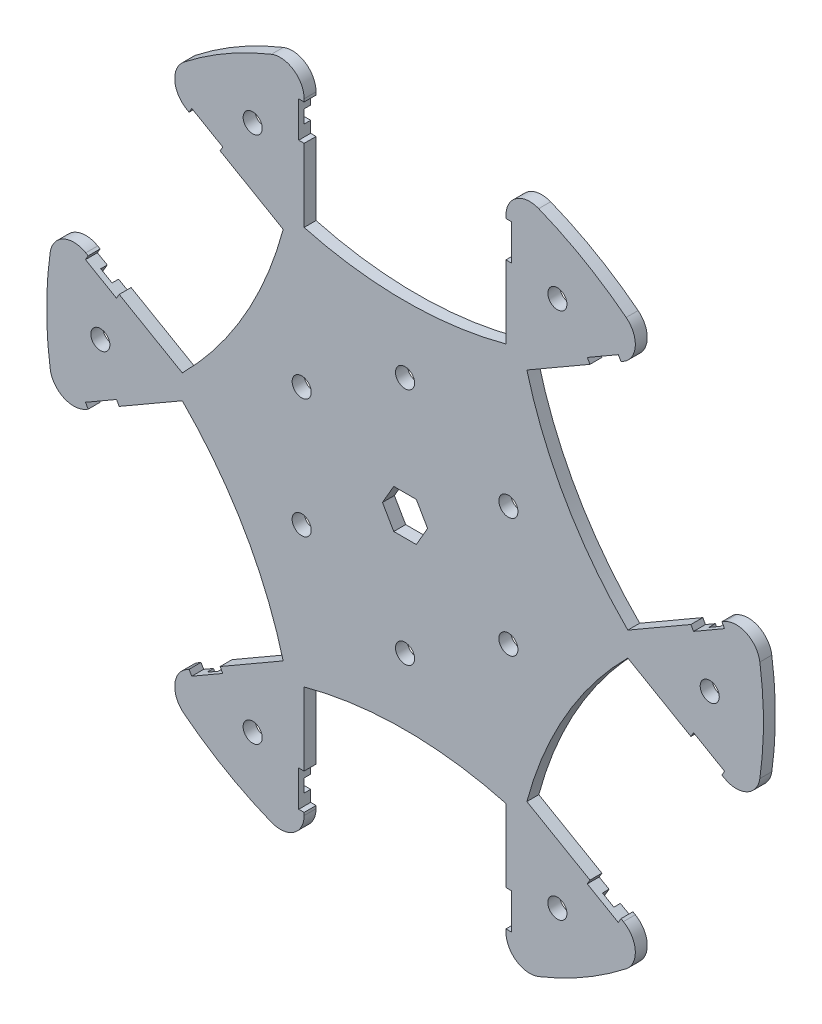
SolidWorks part; units mm, degrees
material "PET"
ref_plane "Front Plane" through (0, 0, 0) normal (0, 0, 1) x (1, 0, 0)
ref_plane "Top Plane" through (0, 0, 0) normal (0, 1, 0) x (1, 0, 0)
ref_plane "Right Plane" through (0, 0, 0) normal (1, 0, 0) x (0, 0, -1)
ref_axis "Axis1" through (0, 0, -6.4917) along (0, 0, 1)
sketch "Sketch2" plane through (0, 0, 0) normal (0, 0, 1) x (1, 0, 0)
  line L6 (56.0628, 0) -> (28.0314, 48.5518)
  line L7 (28.0314, 48.5518) -> (-28.0314, 48.5518)
  line L8 (-28.0314, 48.5518) -> (-56.0628, 0)
  line L9 (-56.0628, 0) -> (-28.0314, -48.5518)
  line L10 (-28.0314, -48.5518) -> (28.0314, -48.5518)
  line L11 (28.0314, -48.5518) -> (56.0628, 0)
  line L12 (56.0628, 0) -> (28.0314, 48.5518)
  line L13 (28.0314, 48.5518) -> (-28.0314, 48.5518)
  line L14 (-28.0314, 48.5518) -> (-56.0628, 0)
  line L15 (-56.0628, 0) -> (-28.0314, -48.5518)
  line L16 (-28.0314, -48.5518) -> (28.0314, -48.5518)
  line L17 (28.0314, -48.5518) -> (56.0628, 0)
  circle A0 centre (0, 0) radius 56.0628 construction
  circle A1 centre (0, 0) radius 56.0628
  circle A2 centre (0, 0) radius 63.4125 construction
  circle A3 centre (0, 0) radius 63.4125
  circle A4 centre (0, 0) radius 65 construction
  circle A5 centre (0, 0) radius 65
  dimension "D1" = 0
sketch "Sketch5" plane through (0, 0, 0) normal (0, 0, 1) x (1, 0, 0)
  line L0 (16.4124, 34.2097) -> (16.4124, 62.8938) construction
  line L1 (16.4124, 34.2097) -> (16.4124, 62.8938)
  line L2 (-16.4124, 62.8938) -> (-16.4124, 34.2097) construction
  line L3 (-16.4124, 62.8938) -> (-16.4124, 34.2097)
  line L4 (0, 48.5518) -> (0, 63.4125) construction
  line L5 (0, 48.5518) -> (0, 63.4125)
  arc A0 (-16.4124, 34.2097) -> (16.4124, 34.2097) centre (0, 97.1035) ccw construction
  arc A1 (-16.4124, 34.2097) -> (16.4124, 34.2097) centre (0, 97.1035) ccw
sketch "Sketch3" plane through (0, 0, 0) normal (0, 0, 1) x (1, 0, 0)
  circle A0 centre (0, 0) radius 60.0628
  circle A1 centre (0, 0) radius 56.0628 construction
  circle A2 centre (0, 0) radius 56.0628 construction
  dimension "D1" = 4
extrude "Disk" add sketch "Sketch3" along normal blind 2
sketch "Sketch4" plane through (0, 0, 0) normal (0, 0, 1) x (1, 0, 0)
  line L0 (28.0314, 48.5518) -> (-28.0314, 48.5518) construction
  line L1 (28.0314, 48.5518) -> (-28.0314, 48.5518) construction
  line L3 (-25.2, 49.6518) -> (25.2, 49.6518)
  line L4 (-25.2, 49.6518) -> (-25.2, 47.4518)
  line L5 (-25.2, 47.4518) -> (25.2, 47.4518)
  line L6 (25.2, 49.6518) -> (25.2, 47.4518)
  line L7 (-25.2, 49.6518) -> (25.2, 47.4518) construction
  line L8 (-25.2, 47.4518) -> (25.2, 49.6518) construction
  point P2 (0, 48.5518)
  dimension "D1" = 2.2
  dimension "D2" = 50.4
extrude "Axle" cut sketch "Sketch4" along normal blind 1.1
sketch "Sketch7" plane through (0, 0, 0) normal (0, 0, 1) x (1, 0, 0)
  line L0 (16.9124, 62.8938) -> (-16.9124, 62.8938)
  line L1 (0, 48.5518) -> (0, 63.4125) construction
  line L2 (16.9124, 62.8938) -> (16.9124, 33.3423)
  line L3 (-16.9124, 62.8938) -> (-16.9124, 33.3423)
  line L4 (-16.4124, 62.8938) -> (-16.4124, 34.2097) construction
  arc A0 (-16.9124, 33.3423) -> (16.9124, 33.3423) centre (0, 96.1035) ccw
  arc A1 (-16.4124, 34.2097) -> (16.4124, 34.2097) centre (0, 97.1035) ccw construction
  arc A2 (-16.4124, 34.2097) -> (16.4124, 34.2097) centre (0, 97.1035) ccw construction
  point P3 (0, 62.8938)
  point P6 (0, 32.1035)
  point P16 (0, 31.1035)
  dimension "D1" = 0.5
  dimension "D3" = 1
  dimension "D2" = 2
extrude "Roller" cut sketch "Sketch7" along normal up to next
sketch "Sketch8" plane through (0, 0, 0) normal (0, 0, 1) x (1, 0, 0)
  line L0 (16.9124, 47.4518) -> (16.9124, 49.6518) construction
  line L1 (16.9124, 47.4518) -> (16.9124, 49.6518) construction
  line L3 (-17.8124, 51.5518) -> (-16.9124, 51.5518)
  line L4 (17.8124, 51.5518) -> (17.8124, 45.5518)
  line L6 (16.9124, 51.5518) -> (16.4124, 51.5518)
  line L8 (16.4124, 51.5518) -> (16.4124, 45.5518)
  line L11 (16.4124, 34.2097) -> (16.4124, 62.8938) construction
  line L12 (16.4124, 34.2097) -> (16.4124, 62.8938) construction
  line L14 (-16.9124, 51.5518) -> (-16.4124, 51.5518)
  line L15 (16.9124, 51.5518) -> (16.9124, 45.5518) construction
  line L16 (16.9124, 33.3423) -> (16.9124, 47.4518) construction
  line L17 (17.8124, 51.5518) -> (16.9124, 51.5518)
  line L18 (17.8124, 45.5518) -> (16.9124, 45.5518)
  line L19 (16.4124, 45.5518) -> (16.9124, 45.5518)
  line L20 (0, 48.5518) -> (0, 63.4125) construction
  line L21 (0, 48.5518) -> (0, 63.4125) construction
  line L22 (-16.4124, 51.5518) -> (-16.4124, 45.5518)
  line L23 (-16.4124, 45.5518) -> (-16.9124, 45.5518)
  line L24 (-17.8124, 45.5518) -> (-16.9124, 45.5518)
  line L25 (-17.8124, 51.5518) -> (-17.8124, 45.5518)
  point P12 (16.9124, 48.5518)
  dimension "D1" = 6
  dimension "D2" = 1.4
extrude "Washer" cut sketch "Sketch8" along normal up to next
fillet "Fillet1" radius 4 2 edges at (16.9124, 57.6325, 1) (-16.9124, 57.6325, 1)
pattern_circular "CirPattern1" count 6 over 360 about axis through (0, 0, -6.4917) along (0, 0, 1) of "Axle", "Roller", "Washer", "Fillet1"
sketch "Sketch9" plane through (0, 0, 2) normal (0, 0, 1) x (1, 0, 0)
  line L0 (0, 0) -> (-30.0314, -52.0159) construction
  arc A0 (41.455, 43.4628) -> (16.9124, 57.6325) centre (0, 0) ccw construction
  circle A1 centre (-25.5314, -44.2216) radius 1.6
  dimension "D1" = 3.2
  dimension "D2" = 9
extrude "Roller screw" cut sketch "Sketch9" against normal up to next
pattern_circular "CirPattern3" count 6 over 360 about axis through (0, 0, -6.4917) along (0, 0, 1) of "Roller screw"
sketch "Sketch10" plane through (0, 0, 0) normal (0, 0, 1) x (1, 0, 0)
  line L0 (0, 0) -> (3.7816, 0) construction
  line L1 (3.7816, 0) -> (1.8908, 3.275)
  line L2 (1.8908, 3.275) -> (-1.8908, 3.275)
  line L3 (-1.8908, 3.275) -> (-3.7816, 0)
  line L4 (-3.7816, 0) -> (-1.8908, -3.275)
  line L5 (-1.8908, -3.275) -> (1.8908, -3.275)
  line L6 (1.8908, -3.275) -> (3.7816, 0)
  line L7 (0, 0) -> (0, 3.275) construction
  circle A0 centre (0, 0) radius 3.275 construction
  dimension "D1" = 6.55
  dimension "D2" = 90
extrude "Hex axle" cut sketch "Sketch10" along normal up to next
sketch "Sketch11" plane through (0, 0, 0) normal (0, 0, 1) x (1, 0, 0)
  line L0 (0, 0) -> (0, 20) construction
  line L1 (0, 0) -> (20, 0) construction
  circle A0 centre (0, 0) radius 20 construction
  circle A1 centre (0, 20) radius 1.6
  dimension "D1" = 3.2
  dimension "D2" = 40
  dimension "D3" = 90
extrude "Hub screws" cut sketch "Sketch11" along normal up to next
pattern_circular "CirPattern4" count 6 over 360 about axis through (0, 0, -6.4917) along (0, 0, 1) of "Hub screws"
equation "\"D1@Sketch10\"=25.4/4+0.2"
